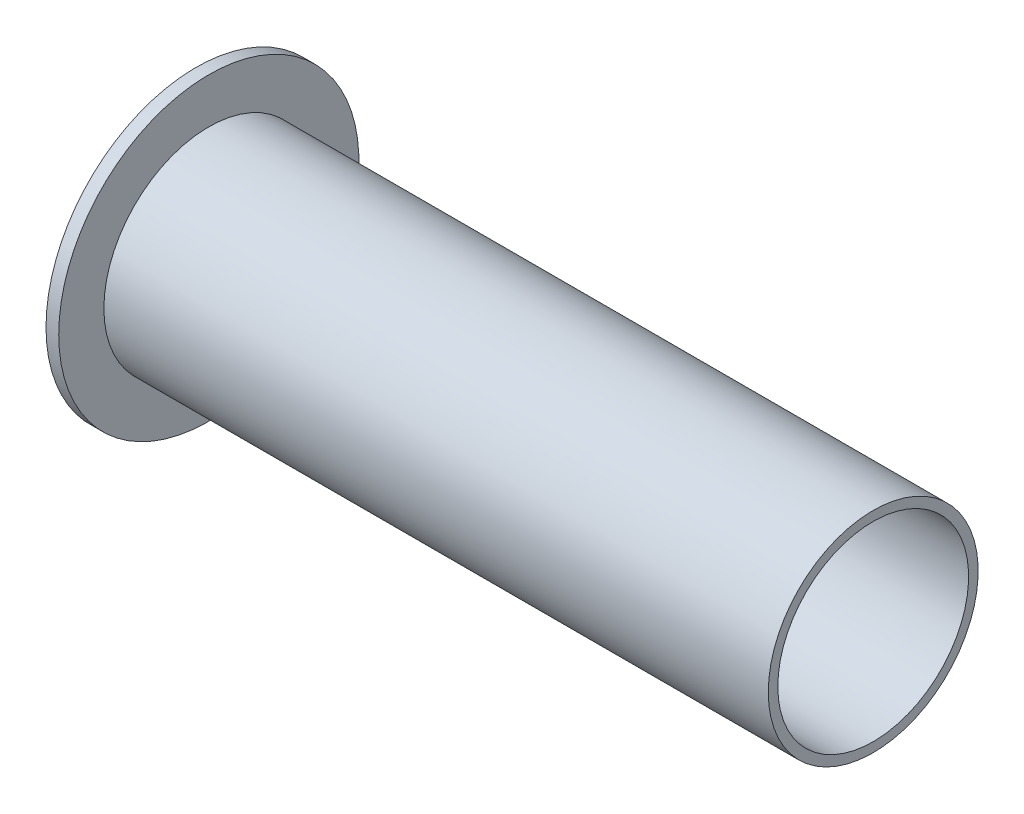
SolidWorks part; units mm, degrees
material "PF"
ref_plane "Plano frontal" through (0, 0, 0) normal (0, 0, 1) x (1, 0, 0)
ref_plane "Plano superior" through (0, 0, 0) normal (0, 1, 0) x (1, 0, 0)
ref_plane "Plano direito" through (0, 0, 0) normal (1, 0, 0) x (0, 0, -1)
sketch "Esboço1" plane through (0, 0, 0) normal (0, 0, 1) x (1, 0, 0)
  line L0 (-52.5, 0) -> (52.5, 0) construction
  line L1 (-51.9615, 23.6) -> (-51.9615, 16.5)
  line L2 (-53.9615, 15) -> (52.5, 15)
  line L3 (52.5, 15) -> (52.5, 16.5)
  line L4 (52.5, 16.5) -> (-51.9615, 16.5)
  line L5 (-53.9615, 15) -> (-53.9615, 23.6)
  line L6 (-53.9615, 23.6) -> (-51.9615, 23.6)
  dimension "D1" = 105
  dimension "D2" = 15
  dimension "D3" = 2
  dimension "D4" = 1.5
  dimension "D6" = 7.1
revolve "Revolução2" add sketch "Esboço1" angle 360 about L0
